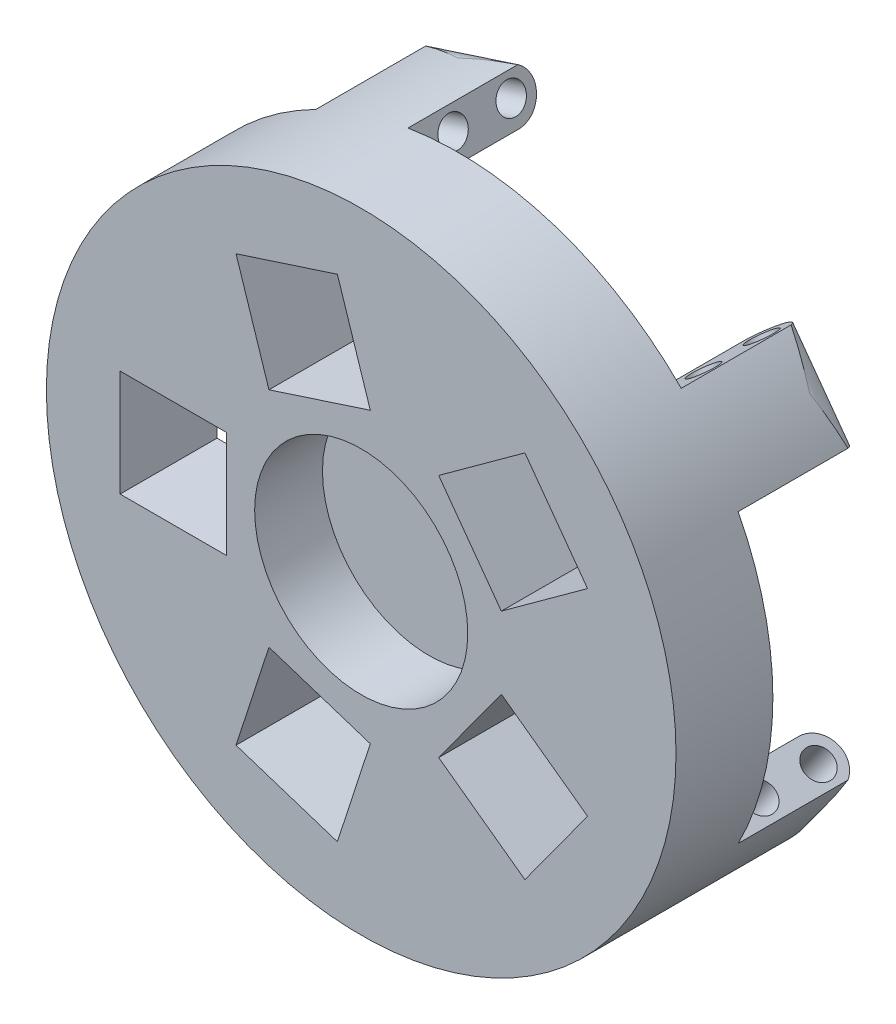
SolidWorks part; units mm, degrees
ref_plane "Plan de face" through (0, 0, 0) normal (0, 0, 1) x (1, 0, 0)
ref_plane "Plan de dessus" through (0, 0, 0) normal (0, 1, 0) x (1, 0, 0)
ref_plane "Plan de droite" through (0, 0, 0) normal (1, 0, 0) x (0, 0, -1)
sketch "Esquisse1" plane through (0, 0, 0) normal (0, 0, 1) x (1, 0, 0)
  circle A0 centre (0, 0) radius 32.5
  dimension "D1" = 65
extrude "Boss.-Extru.1" add sketch "Esquisse1" along normal blind 10
sketch "Esquisse2" plane through (0, 0, 0) normal (0, 1, 0) x (1, 0, 0)
  line L0 (-32.5, 0) -> (-32.5, 10)
  line L1 (-27.5, 0) -> (-27.5, 10)
  line L2 (32.5, 0) -> (-32.5, 0) construction
  line L3 (-32.5, 0) -> (-27.5, 0)
  arc A0 (-32.5, 10) -> (-27.5, 10) centre (-30, 10) cw
  circle A1 centre (-30, 10) radius 1.5
  circle A2 centre (-30, 4) radius 1.5
  dimension "D3" = 3
  dimension "D4" = 3
  dimension "D1" = 10
  dimension "D2" = 5
  dimension "D5" = 6
extrude "Boss.-Extru.2" add sketch "Esquisse2" along normal blind 5 and the other way blind 5
sketch "Esquisse3" plane through (0, 0, 0) normal (0, 0, 1) x (1, 0, 0)
  line L2 (-32.1131, 5) -> (-32.5, 5)
  line L3 (-32.5, 5) -> (-32.5, 0)
  line L4 (-32.1131, 5) -> (-32.5, 5)
  line L5 (-32.5, 5) -> (-32.5, 0)
  line L6 (-32.5, 0) -> (-32.5, -5)
  line L7 (-32.5, -5) -> (-32.1131, -5)
  line L8 (-32.5, 0) -> (-32.5, -5)
  line L9 (-32.5, -5) -> (-32.1131, -5)
  arc A1 (-32.1131, 5) -> (-32.5, 0) centre (0, 0) ccw
  arc A2 (-32.1131, 5) -> (-32.5, 0) centre (0, 0) ccw
  arc A3 (-32.5, 0) -> (-32.1131, -5) centre (0, 0) ccw
  arc A4 (-32.5, 0) -> (-32.1131, -5) centre (0, 0) ccw
  arc M7 (-32.5, 0) -> (-32.1131, 5) centre (0, 0) cw
  line M8 (-32.1131, 5) -> (-32.5, 5)
  line M9 (-32.5, 5) -> (-32.5, 0)
  dimension "D1" = 0
  dimension "D2" = 0
extrude "Enlèv. mat.-Extru.1" cut sketch "Esquisse3" against normal through all contours M9 M7 M8 | A4 L8 L9 region at (-32.384, 3.7515, 0) region at (-32.384, -3.7515, 0)
pattern_circular "Répétition circulaire1" count 5 over 360 about axis through (0, 0, 0) along (0, 0, 1) of "Enlèv. mat.-Extru.1", "Boss.-Extru.2"
sketch "Esquisse4" plane through (0, 0, 0) normal (0, 0, -1) x (-1, 0, 0)
  line L0 (27.5, 0) -> (13.8865, 0) construction
  line L1 (27.5, -5) -> (27.5, 5) construction
  line L2 (32.1131, 5) -> (27.5, 5) construction
  line L3 (13.8865, 5.5) -> (24.8865, 5.5)
  line L4 (13.8865, 5.5) -> (13.8865, -5.5)
  line L5 (13.8865, -5.5) -> (24.8865, -5.5)
  line L6 (24.8865, 5.5) -> (24.8865, -5.5)
  line L7 (13.8865, 5.5) -> (24.8865, -5.5) construction
  line L8 (13.8865, -5.5) -> (24.8865, 5.5) construction
  line L9 (19.3865, 5.5) -> (19.3865, -5.5) construction
  line L16 (24.0115, 5.5) -> (18.7615, 5.5)
  line L21 (24.0115, -5.5) -> (18.7615, -5.5)
  point P5 (19.3865, 0)
  point P10 (19.3865, 7.5)
  point P13 (29.8065, 5)
  point P16 (19.3865, 0)
  dimension "D1" = 11
  dimension "D2" = 11
  dimension "D3" = 10.42
extrude "Enlèv. mat.-Extru.3" cut sketch "Esquisse4" against normal through all contours L6 L3 L4 L5 region at (-19.3865, 0, 0)
pattern_circular "Répétition circulaire2" count 5 over 360 about axis through (0, 0, 0) along (0, 0, 1) of "Enlèv. mat.-Extru.3"
sketch "Esquisse5" plane through (0, 0, 10) normal (0, 0, 1) x (1, 0, 0)
  circle A0 centre (0, 0) radius 11
  dimension "D1" = 22
extrude "Enlèv. mat.-Extru.4" cut sketch "Esquisse5" against normal blind 7
